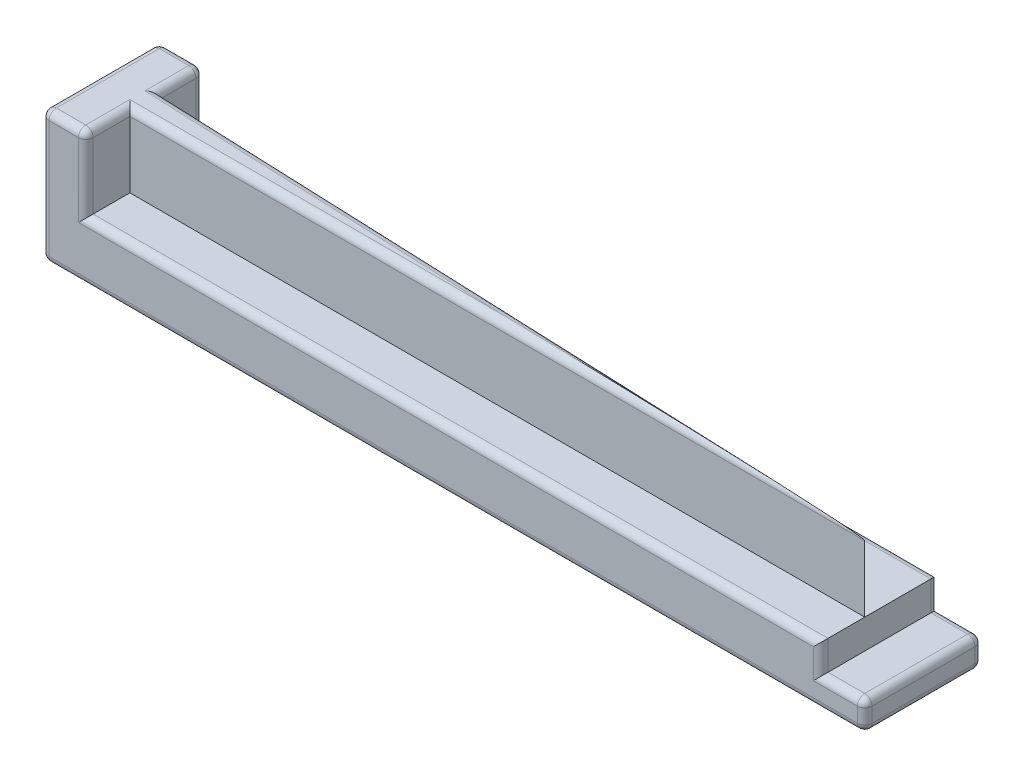
SolidWorks part; units mm, degrees
ref_plane "Front Plane" through (0, 0, 0) normal (0, 0, 1) x (1, 0, 0)
ref_plane "Top Plane" through (0, 0, 0) normal (0, 1, 0) x (1, 0, 0)
ref_plane "Right Plane" through (0, 0, 0) normal (1, 0, 0) x (0, 0, -1)
sketch "Sketch1" plane through (0, 0, 0) normal (0, 1, 0) x (1, 0, 0)
  line L3 (0, 0) -> (50, 0)
  line L4 (50, 0) -> (0, 2)
  line L5 (0, 2) -> (0, 0)
  dimension "D1" = 2
  dimension "D2" = 50
extrude "Boss-Extrude1" add sketch "Sketch1" along normal blind 5
sketch "Sketch2" plane through (0, 0, 0) normal (0, -1, 0) x (1, 0, 0)
  line L1 (-3, 3) -> (53, 3)
  line L2 (-3, 3) -> (-3, -5)
  line L3 (-3, -5) -> (53, -5)
  line L4 (53, 3) -> (53, -5)
  line L5 (0, -2) -> (0, 0) construction
  line L8 (0, 0) -> (50, 0) construction
  point P8 (-3, -1)
  point P13 (0, -1)
  dimension "D1" = 3
  dimension "D2" = 3
  dimension "D3" = 3
extrude "Boss-Extrude2" add sketch "Sketch2" along normal blind 4
sketch "Sketch3" plane through (0, 0, 0) normal (0, 1, 0) x (1, 0, 0)
  line L12 (53, -3) -> (-3, -3) construction
  line L13 (-3, 5) -> (0, 5)
  line L14 (-3, 5) -> (-3, -3)
  line L15 (-3, -3) -> (0, -3)
  line L16 (0, 5) -> (0, -3)
  line L17 (0, 2) -> (0, 0) construction
  line L18 (53, 5) -> (50, 5)
  line L19 (53, 5) -> (53, -3)
  line L20 (53, -3) -> (50, -3)
  line L21 (50, 5) -> (50, -3)
  line M10 (50, 0) -> (0, 0)
  line M12 (-3, 5) -> (-3, -3)
  line M13 (-3, -3) -> (53, -3)
  line M14 (53, -3) -> (53, 5)
  line M15 (53, 5) -> (-3, 5)
extrude "Cut-Extrude2" cut sketch "Sketch3<3>" against normal blind 2 contours L19 M15 M13 M14 region at (51.5, 0, -1)
sketch "Sketch3<3>" plane through (0, 0, 0) normal (0, 1, 0) x (1, 0, 0) same geometry as "Sketch3"
extrude "Boss-Extrude4" add sketch "Sketch3" along normal up to surface (5 mm away) contours L16 M15 M12 M13 M10 region at (-1.5, 0, -1) up to face at (16.6667, 5, -0.6667)
fillet "Fillet1" radius 0.5 24 edges at (53, -2, -1) (53, -4, -1) (-3, -4, -1) (25, -4, -5) (53, -3, -5) (51.5, -2, -5) (50, -1, -5) (25, 0, -5) (0, 2.5, -5) (-3, 0.5, -5) (53, -3, 3) (25, -4, 3) (-3, 0.5, 3) (0, 2.5, 3) (25, 0, 3) (50, -1, 3) (51.5, -2, 3) (25, 5, 0) (0, 5, 1.5) (-1.5, 5, 3) (-3, 5, -1) (-1.5, 5, -5) (0, 5, -3.5) (25, 5, -1)
